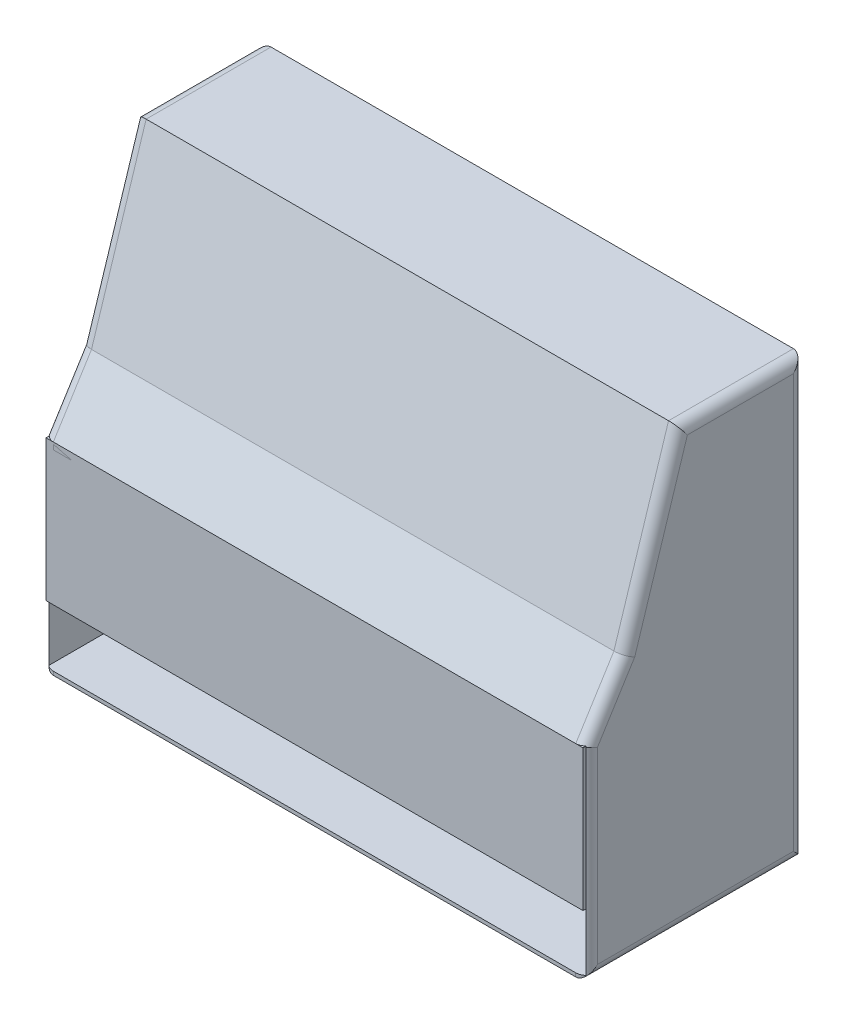
SolidWorks part; units mm, degrees
ref_plane "Front Plane" through (0, 0, 0) normal (0, 0, 1) x (1, 0, 0)
ref_plane "Top Plane" through (0, 0, 0) normal (0, 1, 0) x (1, 0, 0)
ref_plane "Right Plane" through (0, 0, 0) normal (1, 0, 0) x (0, 0, -1)
sketch "Sketch2" plane through (0, 0, 0) normal (0, 1, 0) x (1, 0, 0)
  line L1 (0, 0) -> (1500, 0)
  line L2 (0, 0) -> (0, 600)
  line L3 (0, 600) -> (1500, 600)
  line L4 (1500, 0) -> (1500, 600)
extrude "Boss-Extrude1" add sketch "Sketch2" against normal blind 50
ref_plane "Plane1" through (0, 0, 0) normal (-1, 0, 0) x (0, 0, 1)
ref_plane "Plane6" through (0, 1000, 0) normal (0, 1, 0) x (1, 0, 0)
sketch "Sketch9" plane through (0, 0, 0) normal (-1, 0, 0) x (0, 0, 1)
  line L0 (-600, 0) -> (-600, 1200)
  line L1 (-600, 1200) -> (-255.7946, 1200)
  line L2 (-255.7946, 1200) -> (-105.1966, 725.4437)
  line L5 (-105.1966, 725.4437) -> (0, 557.1426)
  line L6 (0, 557.1426) -> (0, 0)
  line L7 (0, 0) -> (-600, 0)
extrude "Boss-Extrude8" add sketch "Sketch9" against normal blind 1500 separate body contours L7 L1 L0 region at (0, 544.8288, -331.7562)
shell "Shell1" thickness 10 removed face at (750, 278.5713, 0)
fillet "Fillet4" radius 30 12 edges at (0, 600, -600) (0, 1200, -427.8973) (0, 962.7219, -180.4956) (0, 641.2931, -52.5983) (0, 278.5713, 0) (0, 0, -300) (1500, 278.5713, 0) (1500, 641.2931, -52.5983) (1500, 962.7219, -180.4956) (1500, 1200, -427.8973) (1500, 600, -600) (1500, 0, -300)
ref_plane "Plane7" through (0, 0, 0) normal (0, 0, 1) x (1, 0, 0)
sketch "Sketch10" plane through (0, 0, 0) normal (0, 0, 1) x (1, 0, 0)
  line L1 (10, 10) -> (10, 1190) construction
  line L2 (1490, 557.1426) -> (10, 557.1426)
  line L3 (1490, 557.1426) -> (1490, 168.4142)
  line L4 (1490, 168.4142) -> (10, 168.4142)
  line L5 (10, 557.1426) -> (10, 168.4142)
extrude "Boss-Extrude9" add sketch "Sketch10" against normal blind 10 separate body
sketch "Sketch11" plane through (0, 0, 0) normal (0, 1, 0) x (1, 0, 0)
  line L0 (0, 27.5) -> (0, -27.5) construction
  line L1 (0, 0) -> (50, 0)
  line L2 (0, 0) -> (0, 50)
  line L3 (0, 50) -> (50, 50)
  line L4 (50, 0) -> (50, 50)
  line L5 (0, 600) -> (50, 600)
  line L6 (0, 600) -> (0, 550)
  line L7 (0, 550) -> (50, 550)
  line L8 (50, 600) -> (50, 550)
  line L9 (1500, 600) -> (0, 600) construction
  line L10 (-5.5, 0) -> (5.5, 0) construction
  line L11 (1500, 600) -> (1450, 600)
  line L12 (1500, 600) -> (1500, 550)
  line L13 (1500, 550) -> (1450, 550)
  line L14 (1450, 600) -> (1450, 550)
  line L15 (1500, 0) -> (1450, 0)
  line L16 (1500, 0) -> (1500, 50)
  line L17 (1500, 50) -> (1450, 50)
  line L18 (1450, 0) -> (1450, 50)
  line L19 (1500, 0) -> (1500, 600) construction
extrude "Boss-Extrude10" add sketch "Sketch11" against normal blind 700
sketch "Sketch12" plane through (0, 0, 0) normal (0, 0, 1) x (1, 0, 0)
  line L1 (1500, 0) -> (-590.3351, 0)
  line L2 (1500, 0) -> (1500, -1164.4184)
  line L3 (1500, -1164.4184) -> (-590.3351, -1164.4184)
  line L4 (-590.3351, 0) -> (-590.3351, -1164.4184)
extrude "Cut-Extrude1" cut sketch "Sketch12" against normal blind 20000 and the other way blind 20000
